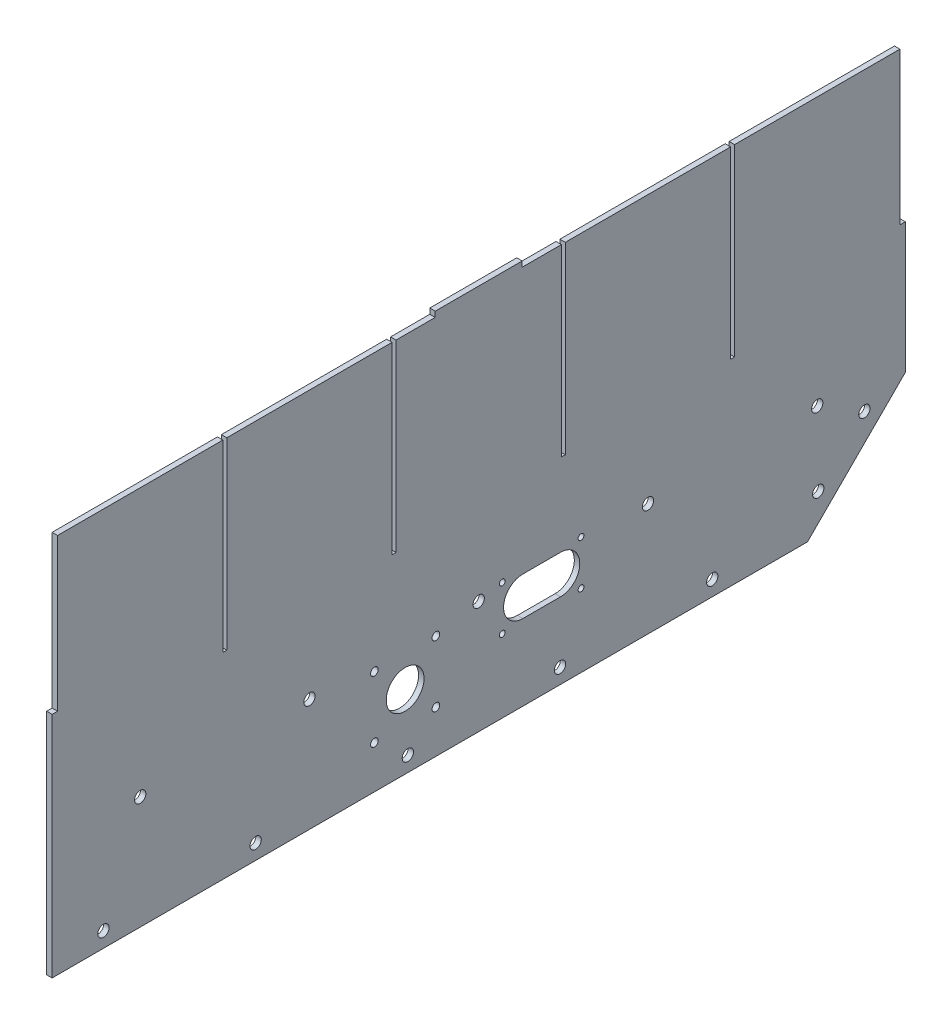
SolidWorks part; units mm, degrees
material "6061-T6 (SS)"
ref_plane "X-Y Datum" through (0, 0, 0) normal (0, 0, 1) x (1, 0, 0)
ref_plane "X-Z Datum" through (0, 0, 0) normal (0, 1, 0) x (1, 0, 0)
ref_plane "Y-Z Datum" through (0, 0, 0) normal (1, 0, 0) x (0, 0, -1)
sketch "Sketch1" plane through (0, 0, 0) normal (1, 0, 0) x (0, 0, -1)
  line L1 (-249.174, 82.55) -> (249.174, 82.55)
  line L2 (-249.174, 82.55) -> (-249.174, -82.55)
  line L3 (-249.174, -82.55) -> (249.174, -82.55)
  line L4 (249.174, 82.55) -> (249.174, -82.55)
  line L5 (-249.174, 82.55) -> (249.174, -82.55) construction
  line L6 (-249.174, -82.55) -> (249.174, 82.55) construction
  point P0 (0, 0)
  dimension "D1" = 165.1
  dimension "D2" = 498.348
extrude "Boss-Extrude1" add sketch "Sketch1" along normal mid plane 3.175
sketch "Sketch2" plane through (1.5875, 0, 0) normal (1, 0, 0) x (0, 0, -1)
  line L2 (249.174, -82.55) -> (192.024, -139.7)
  line L5 (-249.174, -82.55) -> (249.174, -82.55) construction
  line L6 (-249.174, -82.55) -> (249.174, -82.55)
  line L8 (192.024, -139.7) -> (-249.174, -139.7)
  line L9 (-249.174, -139.7) -> (-249.174, -82.55)
  line L11 (-249.174, 82.55) -> (-249.174, -82.55) construction
  line L12 (249.174, -82.55) -> (249.174, 82.55) construction
  line M10 (-249.174, -82.55) -> (249.174, -82.55)
  dimension "D1" = 45
  dimension "D5" = 57.15
extrude "Boss-Extrude2" add sketch "Sketch2" against normal blind 3.175 contours L2 M10 region at (1.5875, -110.5456, 13.9978)
sketch "Sketch3" plane through (-1.5875, 0, 0) normal (-1, 0, 0) x (0, 0, 1)
  line L0 (219.202, -139.7) -> (219.202, -130.81)
  line L1 (-192.024, -139.7) -> (249.174, -139.7) construction
  line L2 (219.202, -130.81) -> (249.174, -130.81)
  line L3 (249.174, 82.55) -> (249.174, -139.7) construction
  circle A0 centre (219.202, -130.81) radius 3.302
  dimension "D1" = 6.604
extrude "Cut-Extrude1" cut sketch "Sketch3" against normal through all contours L0 A0 L2 | L2 A0 L0 region at (-1.5875, -130.3429, 218.7349) region at (-1.5875, -132.2114, 220.6034)
pattern_linear "LPattern1" count 5 spacing 88.9 along (0, 0, -1) of "Cut-Extrude1"
sketch "Sketch4" plane through (-1.5875, 0, 0) normal (-1, 0, 0) x (0, 0, 1)
  line L0 (-206.3924, -125.3316) -> (-198.3102, -117.2494)
  line L1 (-249.174, -82.55) -> (-192.024, -139.7) construction
  line L2 (-192.024, -139.7) -> (-183.9418, -131.6178)
  line L3 (-183.9418, -131.6178) -> (-198.3102, -117.2494)
  circle A0 centre (-198.3102, -117.2494) radius 3.302
  dimension "D1" = 6.604
extrude "Cut-Extrude2" cut sketch "Sketch4" against normal through all and the other way through all contours L3 A0 L0 | L0 A0 L3 region at (-1.5875, -116.5887, -198.3102) region at (-1.5875, -119.2313, -198.3102)
pattern_linear "LPattern2" count 2 spacing 38.1 along (0, 0.7071, -0.7071) of "Cut-Extrude2"
sketch "Sketch5" plane through (1.5875, 0, 0) normal (1, 0, 0) x (0, 0, -1)
  line L1 (249.174, 82.55) -> (245.999, 82.55)
  line L2 (249.174, 82.55) -> (249.174, -6.35)
  line L3 (249.174, -6.35) -> (245.999, -6.35)
  line L4 (245.999, 82.55) -> (245.999, -6.35)
  line L5 (-249.174, 82.55) -> (-245.999, 82.55)
  line L6 (-249.174, 82.55) -> (-249.174, -6.35)
  line L7 (-249.174, -6.35) -> (-245.999, -6.35)
  line L8 (-245.999, 82.55) -> (-245.999, -6.35)
  dimension "D1" = 3.175
  dimension "D2" = 88.9
  dimension "D3" = 3.175
  dimension "D4" = 88.9
extrude "Cut-Extrude3" cut sketch "Sketch5" against normal through all
sketch "Sketch6" plane through (1.5875, 0, 0) normal (1, 0, 0) x (0, 0, -1)
  line L1 (149.4282, -24.892) -> (149.4282, 82.55) construction
  line L2 (122.174, 82.55) -> (249.174, 82.55)
  line L3 (149.4282, -24.892) -> (149.4282, 82.55)
  line L5 (149.4282, 82.55) -> (147.1422, 82.55)
  line L6 (149.4282, 82.55) -> (149.4282, -24.892)
  line L7 (149.4282, -24.892) -> (147.1422, -24.892)
  line L8 (147.1422, 82.55) -> (147.1422, -24.892)
  dimension "D1" = 2.286
  dimension "D2" = 107.442
extrude "Cut-Extrude4" cut sketch "Sketch6" against normal through all contours L2 L8 L7 L3 region at (1.5875, 28.829, -148.2852)
pattern_linear "LPattern3" count 4 spacing 98.8568 along (0, 0, 1) of "Cut-Extrude4"
sketch "Sketch8" plane through (1.5875, 0, 0) normal (1, 0, 0) x (0, 0, -1)
  line L0 (122.174, 85.725) -> (25.4, 85.725) construction
  line L1 (25.4, 82.55) -> (-25.4, 82.55)
  line L2 (25.4, 82.55) -> (25.4, 85.725)
  line L3 (25.4, 85.725) -> (-25.4, 85.725)
  line L4 (-25.4, 82.55) -> (-25.4, 85.725)
  line L5 (25.4, 82.55) -> (-25.4, 85.725) construction
  line L6 (25.4, 85.725) -> (-25.4, 82.55) construction
  point P0 (0, 84.1375)
  dimension "D1" = 3.175
  dimension "D2" = 50.8
extrude "Boss-Extrude3" add sketch "Sketch8" against normal blind 3.175
sketch "Sketch9" plane through (1.5875, 0, 0) normal (1, 0, 0) x (0, 0, -1)
  line L0 (-249.174, -6.35) -> (-249.174, -139.7) construction
  line L1 (192.024, -139.7) -> (-249.174, -139.7) construction
  circle A0 centre (-42.9768, -96.7994) radius 11.05
  dimension "D3" = 22.1
  dimension "D1" = 206.1972
  dimension "D2" = 42.9006
extrude "Cut-Extrude5" cut sketch "Sketch9" against normal through all
sketch "Sketch10" plane through (1.5875, 0, 0) normal (1, 0, 0) x (0, 0, -1)
  line L0 (192.024, -139.7) -> (-249.174, -139.7) construction
  circle A0 centre (0, -73.8124) radius 3
  dimension "D2" = 6
  dimension "D1" = 65.8876
hole_wizard "M6 Clearance Hole1" positions "Sketch11" profile "Sketch12" hole size "M6" standard "ANSI Metric" end condition through all
sketch "Sketch11" plane through (1.5875, 0, 0) normal (1, 0, 0) x (0, 0, -1)
  point P0 (0, -73.8124)
sketch "Sketch12" plane through (1.5875, -73.8124, 0) normal (0, 1, 0) x (0, 0, -1)
  line L0 (0, 0) -> (0, 3.175)
  line L1 (0, 3.175) -> (3.3, 3.175)
  line L2 (3.3, 3.175) -> (3.3, 0)
  line L5 (3.3, 0) -> (0, 0)
  line L11 (0, -6.35) -> (0, 107.95) construction
  dimension "Thru Hole Dia." = 6.6
  dimension "Thru Hole Depth" = 3.175
pattern_linear "LPattern4" count 3 spacing 98.8568 along (0, 0, 1) count 3 spacing 98.8568 along (0, 0, -1) of "M6 Clearance Hole1"
sketch "Sketch14" plane through (1.5875, 0, 0) normal (1, 0, 0) x (0, 0, -1)
  line L0 (192.024, -139.7) -> (-249.174, -139.7) construction
  line L1 (59.7662, -97.1042) -> (13.7662, -97.1042)
  line L2 (59.7662, -97.1042) -> (59.7662, -71.1042)
  line L3 (59.7662, -71.1042) -> (13.7662, -71.1042)
  line L4 (13.7662, -97.1042) -> (13.7662, -71.1042)
  line L5 (59.7662, -97.1042) -> (13.7662, -71.1042) construction
  line L6 (59.7662, -71.1042) -> (13.7662, -97.1042) construction
  line L7 (249.174, -82.55) -> (249.174, -6.35) construction
  line L8 (59.7662, -84.1042) -> (13.7662, -84.1042) construction
  line L9 (-25.0163, -114.7599) -> (-60.9373, -114.7599)
  line L10 (-25.0163, -114.7599) -> (-25.0163, -78.8389)
  line L11 (-25.0163, -78.8389) -> (-60.9373, -78.8389)
  line L12 (-60.9373, -114.7599) -> (-60.9373, -78.8389)
  line L13 (-25.0163, -114.7599) -> (-60.9373, -78.8389) construction
  line L14 (-25.0163, -78.8389) -> (-60.9373, -114.7599) construction
  line L15 (47.7662, -84.1042) -> (25.7662, -84.1042)
  line L16 (47.7662, -95.3542) -> (25.7662, -95.3542)
  line L17 (47.7662, -72.8542) -> (25.7662, -72.8542)
  arc A1 (47.7662, -95.3542) -> (47.7662, -72.8542) centre (47.7662, -84.1042) ccw
  arc A2 (25.7662, -72.8542) -> (25.7662, -95.3542) centre (25.7662, -84.1042) ccw
  point P0 (36.7662, -84.1042)
  point P10 (-42.9768, -96.7994)
  point P20 (36.7662, -84.1042)
  dimension "D7" = 11.25
  dimension "D1" = 46
  dimension "D2" = 26
  dimension "D3" = 42.5958
  dimension "D4" = 189.4078
  dimension "D5" = 35.921
  dimension "D6" = 22
hole_wizard "M4 Clearance Hole1" positions "Sketch17" profile "Sketch18" hole size "M4" standard "ANSI Metric" end condition through all
sketch "Sketch17" plane through (1.5875, 0, 0) normal (1, 0, 0) x (0, 0, -1)
  point P0 (-25.0163, -78.8389)
  point P3 (-60.9373, -78.8389)
  point P6 (-60.9373, -114.7599)
  point P9 (-25.0163, -114.7599)
sketch "Sketch18" plane through (1.5875, -78.8389, 25.0163) normal (0, 1, 0) x (0, 0, -1)
  line L0 (0, 0) -> (0, 3.175)
  line L1 (0, 3.175) -> (2.25, 3.175)
  line L2 (2.25, 3.175) -> (2.25, 0)
  line L5 (2.25, 0) -> (0, 0)
  line L11 (0, -6.35) -> (0, 107.95) construction
  dimension "Thru Hole Dia." = 4.5
  dimension "Thru Hole Depth" = 3.175
extrude "Cut-Extrude6" cut sketch "Sketch14" against normal through all contours L17 A2 L16 A1 region at (1.5875, -94.8556, -36.7662)
hole_wizard "M3 Clearance Hole1" positions "Sketch19" profile "Sketch20" hole size "M3" standard "ANSI Metric" end condition through all
sketch "Sketch19" plane through (1.5875, 0, 0) normal (1, 0, 0) x (0, 0, -1)
  point P0 (59.7662, -97.1042)
  point P3 (59.7662, -71.1042)
  point P6 (13.7662, -71.1042)
  point P9 (13.7662, -97.1042)
sketch "Sketch20" plane through (1.5875, -97.1042, -59.7662) normal (0, 1, 0) x (0, 0, -1)
  line L0 (0, 0) -> (0, 3.175)
  line L1 (0, 3.175) -> (1.7, 3.175)
  line L2 (1.7, 3.175) -> (1.7, 0)
  line L5 (1.7, 0) -> (0, 0)
  line L11 (0, -6.35) -> (0, 107.95) construction
  dimension "Thru Hole Dia." = 3.4
  dimension "Thru Hole Depth" = 3.175
